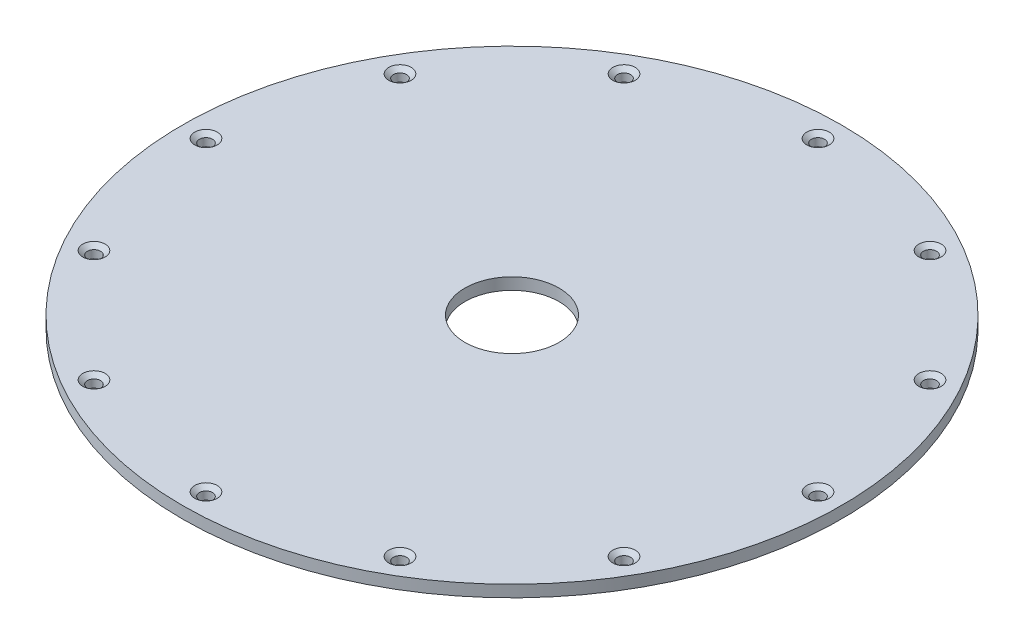
SolidWorks part; units mm, degrees
material "6063-T6"
ref_plane "Front Plane" through (0, 0, 0) normal (0, 0, 1) x (1, 0, 0)
ref_plane "Top Plane" through (0, 0, 0) normal (0, 1, 0) x (1, 0, 0)
ref_plane "Right Plane" through (0, 0, 0) normal (1, 0, 0) x (0, 0, -1)
ref_axis "Axis1" through (0, 55, 0) along (0, -1, 0)
sketch "Sketch1" plane through (0, 0, 0) normal (0, 0, 1) x (1, 0, 0)
  line L0 (-44.45, 0) -> (-6.35, 0)
  line L1 (0, 55) -> (0, -55) construction
  line L2 (-44.45, 0) -> (-44.45, 1.5875)
  line L3 (-44.45, 1.5875) -> (-6.35, 1.5875)
  line L4 (-44.45, 1.5875) -> (-6.35, 1.5875) construction
  line L5 (-6.35, 1.5875) -> (-6.35, 0)
  line L6 (-6.35, 0) -> (0, 0) construction
  line L7 (-44.45, 0) -> (-44.45, 1.5875) construction
  line L8 (-6.35, 1.5875) -> (-6.35, 0) construction
  point P1 (-6.35, 0)
  point P3 (-6.35, 8.9431)
  point P4 (-6.35, 1.5875)
  point P9 (0, 0)
  point P12 (-6.6434, 1.5875)
  point P13 (0, 0)
  point P16 (0, 0)
  point P17 (0, 0)
  point P18 (0, 0)
  point P19 (0, 0)
  point P21 (0, 0)
  point P22 (0, 0)
  point P23 (0, 0)
  point P24 (0, 0)
  point P25 (0, 0)
  point P26 (0, 0)
  point P28 (0, 0)
  point P29 (0, 0)
  point P30 (-6.6747, 0)
revolve "Revolve1" add sketch "Sketch1" angle 360 about axis through (0, 55, 0) along (0, -1, 0)
ref_plane "Hole Location Plane" through (0, 3.175, 0) normal (0, 1, 0) x (1, 0, 0)
sketch "Hole Location" plane through (0, 3.175, 0) normal (0, 1, 0) x (1, 0, 0)
  line L0 (0, 0) -> (-41.275, 0) construction
  circle A0 centre (0, 0) radius 41.275 construction
  dimension "D1" = 82.55
hole_wizard "CSK for #0 Flat Head Machine Screw (100)1" positions "Sketch4" profile "Sketch5" countersink size "#0" standard "ANSI Inch" end condition through all
sketch "Sketch4" plane through (0, 1.5875, 0) normal (0, 1, 0) x (1, 0, 0)
  point P0 (-41.275, 0)
sketch "Sketch5" plane through (-41.275, 1.5875, 0) normal (1, 0, 0) x (0, 0, 1)
  line L0 (0, 0) -> (0, 1.5875)
  line L1 (0, 1.5875) -> (0.889, 1.5875)
  line L2 (0.889, 1.5875) -> (0.889, 0.5222)
  line L3 (0.889, 0.5222) -> (1.5113, 0)
  line L5 (1.5113, 0) -> (0, 0)
  line L6 (-0.889, 0.5222) -> (-1.5113, 0) construction
  line L11 (0, -6.35) -> (0, 107.95) construction
  dimension "Thru Hole Dia." = 1.778
  dimension "Thru Hole Depth" = 1.5875
  dimension "Near C'Sink Dia." = 3.0226
  dimension "Near C'Sink Angle" = 100
pattern_circular "CirPattern1" count 12 every 30 about axis through (0, 55, 0) along (0, -1, 0) of "CSK for #0 Flat Head Machine Screw (100)1"
equation "\"D1@Hole Location\"=\"TANK DIAMETER@Cryo Tank.Assembly\"+\"GASKET SEAT THICKNESS@Cryo Tank.Assembly\""
